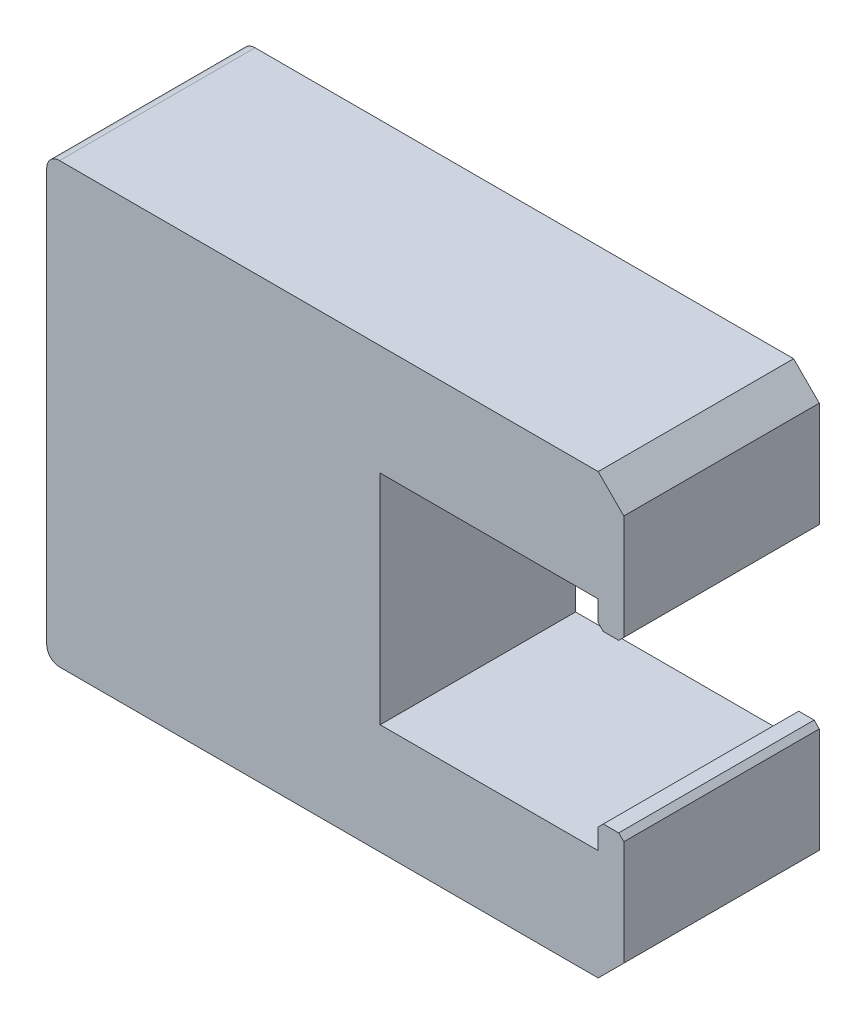
SolidWorks part; units mm, degrees
ref_plane "Front Plane" through (0, 0, 0) normal (0, 0, 1) x (1, 0, 0)
ref_plane "Top Plane" through (0, 0, 0) normal (0, 1, 0) x (1, 0, 0)
ref_plane "Right Plane" through (0, 0, 0) normal (1, 0, 0) x (0, 0, -1)
ref_axis "Axis1" through (0, 0, -88.99) along (0, 0, 1)
ref_axis "Axis2" through (0, -55, 0) along (0, 1, 0)
ref_axis "Axis3" through (-88.99, 0, 0) along (1, 0, 0)
sketch "Sketch1" plane through (0, 0, 0) normal (0, 0, 1) x (1, 0, 0)
  line L0 (0, 0) -> (225, 0)
  line L1 (225, 0) -> (225, 53)
  line L2 (215, 43) -> (130, 43)
  line L3 (215, 43) -> (215, 53)
  line L4 (215, 53) -> (225, 53)
  line L5 (0, 0) -> (0, 171)
  line L6 (215, 128) -> (215, 118)
  line L7 (215, 118) -> (225, 118)
  line L8 (0, 171) -> (225, 171)
  line L9 (225, 171) -> (225, 118)
  line L10 (215, 128) -> (130, 128)
  line L11 (130, 128) -> (130, 43)
  dimension "D1" = 85
  dimension "D2" = 130
  dimension "D3" = 43
  dimension "D4" = 85
  dimension "D5" = 43
  dimension "D6" = 10
  dimension "D7" = 10
extrude "Boss-Extrude1" add sketch "Sketch1" along normal mid plane 76.2
chamfer "Chamfer1" distance 10 angle 45 2 edges at (225, 0, 0) (225, 171, 0)
chamfer "Chamfer2" distance 2 angle 45 4 edges at (215, 118, 0) (215, 53, 0) (225, 118, 0) (225, 53, 0)
fillet "Fillet1" radius 5 2 edges at (0, 171, 0) (0, 0, 0)
